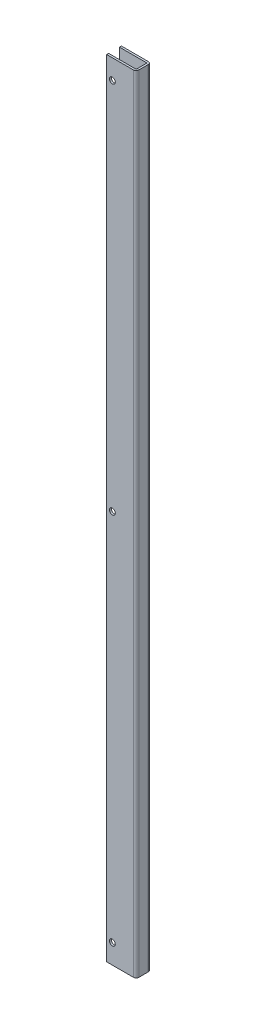
SolidWorks part; units mm, degrees
note: The reader was unsure of these and kept them because the rebuilt part matched: thickness of "Base-Flange1", "Edge-Flange1", "Edge-Flange2", "Sheet-Metal1", "Sheet-Metal2", "Sheet-Metal3", "Sheet-Metal4"; flange length of "Edge-Flange1", "Edge-Flange2".
material "2024-O"
ref_plane "Front Plane" through (0, 0, 0) normal (0, 0, 1) x (1, 0, 0)
ref_plane "Top Plane" through (0, 0, 0) normal (0, 1, 0) x (1, 0, 0)
ref_plane "Right Plane" through (0, 0, 0) normal (1, 0, 0) x (0, 0, -1)
sketch "Sketch1" plane through (0, 0, 0) normal (0, 0, 1) x (1, 0, 0)
  line L1 (15, -400) -> (-15, -400)
  line L2 (15, -400) -> (15, 400)
  line L3 (15, 400) -> (-15, 400)
  line L4 (-15, -400) -> (-15, 400)
  line L5 (15, -400) -> (-15, 400) construction
  line L6 (15, 400) -> (-15, -400) construction
  point P0 (0, 0)
  dimension "D1" = 800
  dimension "D2" = 30
base flange "Base-Flange1" sketch "Sketch1" thickness 2 reverse thickness direction no parameters "D1"=0.7366
edge flange "Edge-Flange1" sketch "Sketch8" flange angle 90 flange length 15 flange position material inside bend radius 0.7366 thickness 2 relief rectangular parameters "D6"=10
sketch "Sketch8" plane through (15, 0, 0) normal (1, 0, 0) x (0, 1, 0)
  line L2 (-400, 0) -> (-400, 13)
  line L3 (-400, 13) -> (400, 13)
  line L4 (400, 13) -> (400, 0)
  line L7 (-400, 0) -> (400, 0) construction
  line L8 (-400, 0) -> (400, 0)
bend "EdgeBend1" bend radius 0.7366 bend angle 90 parameters "D5"=1
edge flange "Edge-Flange2" sketch "Sketch11" flange angle 90 flange length 30 flange position material inside bend radius 0.7366 thickness 2 relief rectangular parameters "D6"=10
sketch "Sketch11" plane through (13, 0, 13) normal (0, 0, 1) x (0, 1, 0)
  line L0 (400, 0) -> (-400, 0) construction
  line L1 (400, 0) -> (-400, 0)
  line L2 (-400, 0) -> (-400, 28)
  line L3 (-400, 28) -> (400, 28)
  line L4 (400, 28) -> (400, 0)
bend "EdgeBend2" bend radius 0.7366 bend angle 90 parameters "D5"=2
sketch "Sketch12" plane through (0, 0, -2) normal (0, 0, -1) x (-1, 0, 0)
  circle A0 centre (9.26, 380) radius 3 construction
  circle A1 centre (9.26, 0) radius 3 construction
  circle A2 centre (9.26, -380) radius 3 construction
  circle A3 centre (9.26, 380) radius 3
  circle A4 centre (9.26, 0) radius 3
  circle A5 centre (9.26, -380) radius 3
extrude "Cut-Extrude1" cut sketch "Sketch12" against normal through all normal cut yes
sketch "Bend-Lines1" [suppressed] plane through (0, 0, 0) normal (0, 1, 0) x (1, 0, 0)
sketch "Bounding-Box1" [suppressed] plane through (0, 0, 0) normal (0, 1, 0) x (1, 0, 0)
sheet metal parameters "Sheet-Metal1" thickness 2 parameters "D1"=0.7366
flat pattern "Flat-Pattern1" [suppressed]
sketch "Bend-Lines2" plane through (0, 0, 0) normal (0, 1, 0) x (1, 0, 0)
sketch3d "Bounding-Box2" [suppressed]
  line L0 (-25, 400, 0) -> (-25, -400, 0) construction
  line L1 (25, 400, 0) -> (25, -400, 0) construction
  line L2 (-25, 400, 0) -> (25, 400, 0) construction
  line L3 (-25, -400, 0) -> (25, -400, 0) construction
sheet metal parameters "Sheet-Metal2" thickness 2 parameters "D1"=0.7366, "D7"=0.5
flat pattern "Flat-Pattern1"
sketch "Bend-Lines2" plane through (0, 0, 0) normal (0, 0, 1) x (1, 0, 0)
  line L0 (24.5383, -400) -> (24.5383, 400) construction
  line L1 (24.5383, -400) -> (24.5383, 400) construction
sketch3d "Bounding-Box2" [suppressed]
  line L0 (34.0765, 400, 0) -> (34.0765, -400, 0) construction
  line L1 (-25, 400, 0) -> (-25, -400, 0) construction
  line L2 (34.0765, 400, 0) -> (-25, 400, 0) construction
  line L3 (34.0765, -400, 0) -> (-25, -400, 0) construction
bend of the flat pattern "Flatten-<EdgeBend1>1"
sheet metal parameters "Sheet-Metal3" thickness 2 parameters "D1"=0.7366, "D7"=0.5
flat pattern "Flat-Pattern1"
sketch "Bend-Lines2" plane through (0, 0, 0) normal (0, 0, 1) x (1, 0, 0)
  line L0 (13.6273, -400) -> (13.6273, 400) construction
  line L1 (13.6273, -400) -> (13.6273, 400) construction
  line L2 (25.882, -400) -> (25.882, 400) construction
  line L3 (25.882, -400) -> (25.882, 400) construction
sketch3d "Bounding-Box2" [suppressed]
  line L0 (54.5093, 400, 0) -> (54.5093, -400, 0) construction
  line L1 (-15, 400, 0) -> (-15, -400, 0) construction
  line L2 (54.5093, 400, 0) -> (-15, 400, 0) construction
  line L3 (54.5093, -400, 0) -> (-15, -400, 0) construction
bend of the flat pattern "Flatten-<EdgeBend1>1"
bend of the flat pattern "Flatten-<EdgeBend2>1"
sheet metal parameters "Sheet-Metal4" thickness 2 parameters "D1"=0.7366, "D7"=0.5
flat pattern "Flat-Pattern1"
sketch "Bend-Lines2" plane through (0, 0, 0) normal (0, 0, 1) x (1, 0, 0)
  line L0 (13.6273, -400) -> (13.6273, 400) construction
  line L1 (13.6273, -400) -> (13.6273, 400) construction
  line L2 (25.882, -400) -> (25.882, 400) construction
  line L3 (25.882, -400) -> (25.882, 400) construction
sketch3d "Bounding-Box2" [suppressed]
  line L0 (54.5093, 400, 0) -> (54.5093, -400, 0) construction
  line L1 (-15, 400, 0) -> (-15, -400, 0) construction
  line L2 (54.5093, 400, 0) -> (-15, 400, 0) construction
  line L3 (54.5093, -400, 0) -> (-15, -400, 0) construction
bend of the flat pattern "Flatten-<EdgeBend1>1"
bend of the flat pattern "Flatten-<EdgeBend2>1"
